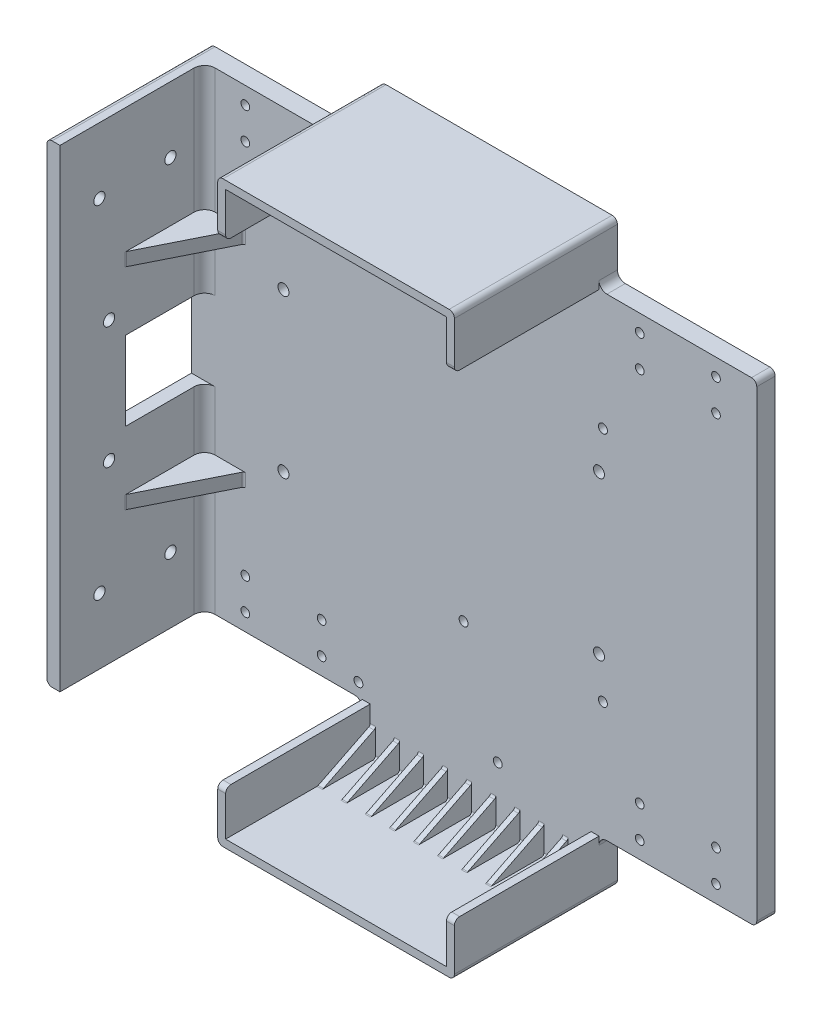
SolidWorks part; units mm, degrees
ref_plane "Front Plane" through (0, 0, 0) normal (0, 0, 1) x (1, 0, 0)
ref_plane "Top Plane" through (0, 0, 0) normal (0, 1, 0) x (1, 0, 0)
ref_plane "Right Plane" through (0, 0, 0) normal (1, 0, 0) x (0, 0, -1)
sketch "Sketch2" plane through (0, 0, 0) normal (0, 0, 1) x (1, 0, 0)
  line L1 (-105, -90) -> (105, -90)
  line L2 (-105, -90) -> (-105, 90)
  line L3 (-105, 90) -> (105, 90)
  line L4 (105, -90) -> (105, 90)
  line L5 (-105, -90) -> (105, 90) construction
  line L6 (-105, 90) -> (105, -90) construction
  point P0 (0, 0)
  dimension "D1" = 210
  dimension "D2" = 180
extrude "Boss-Extrude1" add sketch "Sketch2" along normal blind 7
sketch "Sketch3" plane through (0, -90, 0) normal (0, -1, 0) x (-1, 0, 0)
  line L0 (105, -7) -> (-105, -7) construction
  line L1 (45, -7) -> (-45, -7)
  line L2 (45, -7) -> (45, 0)
  line L3 (45, 0) -> (-45, 0)
  line L4 (-45, -7) -> (-45, 0)
  line L5 (105, 0) -> (-105, 0) construction
  line L6 (105, -7) -> (105, 0) construction
  dimension "D1" = 90
  dimension "D2" = 60
extrude "Boss-Extrude2" add sketch "Sketch3" along normal blind 20
sketch "Sketch4" plane through (0, 90, 0) normal (0, 1, 0) x (1, 0, 0)
  line L0 (105, 0) -> (-105, 0) construction
  line L1 (-45, 0) -> (45, 0)
  line L2 (-45, 0) -> (-45, -7)
  line L3 (-45, -7) -> (45, -7)
  line L4 (45, 0) -> (45, -7)
  line L5 (105, -7) -> (-105, -7) construction
  line L6 (-105, -7) -> (-105, 0) construction
  dimension "D1" = 90
  dimension "D2" = 60
extrude "Boss-Extrude3" add sketch "Sketch4" along normal blind 20
sketch "Sketch5" plane through (0, 0, 7) normal (0, 0, 1) x (1, 0, 0)
  line L0 (105, 90) -> (45, 90) construction
  line L1 (105, -90) -> (105, 90) construction
  line L2 (0, -1000) -> (0, 49000) construction
  line L3 (-1000, 0) -> (49000, 0) construction
  line L4 (-45, 110) -> (45, 110) construction
  line L5 (45, -110) -> (-45, -110) construction
  line L6 (-105, 90) -> (-105, -90) construction
  circle A0 centre (89.5, 83.5) radius 1.65
  circle A2 centre (89.5, 71.5) radius 1.65
  circle A3 centre (60.5, 83.5) radius 1.65
  circle A5 centre (60.5, 71.5) radius 1.65
  circle A6 centre (-60.5, 71.5) radius 1.65
  circle A8 centre (-60.5, 83.5) radius 1.65
  circle A9 centre (-89.5, 71.5) radius 1.65
  circle A11 centre (-89.5, 83.5) radius 1.65
  circle A12 centre (-89.5, -83.5) radius 1.65
  circle A14 centre (-89.5, -71.5) radius 1.65
  circle A15 centre (-60.5, -83.5) radius 1.65
  circle A17 centre (-60.5, -71.5) radius 1.65
  circle A18 centre (60.5, -71.5) radius 1.65
  circle A20 centre (60.5, -83.5) radius 1.65
  circle A21 centre (89.5, -71.5) radius 1.65
  circle A23 centre (89.5, -83.5) radius 1.65
  circle A24 centre (45, 30) radius 2.1
  circle A25 centre (45, -30) radius 2.1
  circle A26 centre (-75, 30) radius 2.1
  circle A27 centre (-75, -30) radius 2.1
  circle A28 centre (-46.5, -85) radius 1.7
  circle A29 centre (-6.5, -45) radius 1.7
  circle A30 centre (6.5, -85) radius 1.7
  circle A31 centre (46.5, -45) radius 1.7
  circle A32 centre (46.5, 45) radius 1.7
  circle A33 centre (6.5, 85) radius 1.7
  circle A34 centre (-6.5, 45) radius 1.7
  circle A35 centre (-46.5, 85) radius 1.7
  dimension "D7" = 3.3
  dimension "D8" = 3.4
  dimension "D9" = 3.3
  dimension "D12" = 60
  dimension "D14" = 4.2
  dimension "D17" = 4.2
  dimension "D20" = 4.2
  dimension "D21" = 4.2
  dimension "D26" = 3.4
  dimension "D29" = 3.4
  dimension "D32" = 3.4
  dimension "D1" = 6.5
  dimension "D2" = 15.5
  dimension "D3" = 58.5
  dimension "D4" = 12
  dimension "D5" = 15.5
  dimension "D6" = 25
  dimension "D11" = 29
  dimension "D13" = 80
  dimension "D15" = 60
  dimension "D16" = 80
  dimension "D18" = 120
  dimension "D19" = 120
  dimension "D22" = 30
  dimension "D23" = 30
  dimension "D24" = 65
  dimension "D25" = 98.5
  dimension "D27" = 25
  dimension "D28" = 98.5
  dimension "D30" = 65
  dimension "D31" = 58.5
  dimension "D10" = 2
extrude "Cut-Extrude1" cut sketch "Sketch5" against normal through all
sketch "Sketch10" plane through (0, 0, 7) normal (0, 0, 1) x (1, 0, 0)
  line L0 (45, 110) -> (45, 90) construction
  line L1 (-105, 90) -> (-110, 90)
  line L2 (-105, 90) -> (-105, -90)
  line L3 (-105, -90) -> (-110, -90)
  line L4 (-110, 90) -> (-110, -90)
  line L5 (-45, 110) -> (45, 110)
  line L6 (-45, 110) -> (-45, 107)
  line L7 (-45, 107) -> (45, 107)
  line L8 (45, 110) -> (45, 107)
  line L9 (-45, -110) -> (-45, -90) construction
  line L10 (45, -110) -> (-45, -110)
  line L11 (45, -110) -> (45, -107)
  line L12 (45, -107) -> (-45, -107)
  line L13 (-45, -110) -> (-45, -107)
  line L15 (-45, 110) -> (-42, 110)
  line L16 (-45, 110) -> (-45, 90)
  line L17 (-45, 90) -> (-42, 90)
  line L18 (-42, 110) -> (-42, 90)
  line L19 (45, 110) -> (42, 110)
  line L20 (45, 110) -> (45, 90)
  line L21 (45, 90) -> (42, 90)
  line L22 (42, 110) -> (42, 90)
  line L23 (-45, -110) -> (-42, -110)
  line L24 (-45, -110) -> (-45, -90)
  line L25 (-45, -90) -> (-42, -90)
  line L26 (-42, -110) -> (-42, -90)
  line L27 (45, -110) -> (42, -110)
  line L28 (45, -110) -> (45, -90)
  line L29 (45, -90) -> (42, -90)
  line L30 (42, -110) -> (42, -90)
  dimension "D1" = 5
  dimension "D2" = 180
  dimension "D3" = 3
  dimension "D4" = 3
  dimension "D5" = 3
  dimension "D6" = 3
  dimension "D7" = 3
  dimension "D8" = 3
  dimension "D9" = 20
  dimension "D10" = 20
  dimension "D11" = 20
  dimension "D12" = 20
extrude "Boss-Extrude4" add sketch "Sketch10" along normal blind 55 contours L2 L1 L4 L3 | L16 L15 L18 L17 | L20 L19 L22 L21 | L6 L5 L8 L7 | L11 L10 L13 L12 | L24 L23 L26 L25 | L28 L27 L30 L29
sketch "Sketch12" plane through (0, 0, 7) normal (0, 0, -1) x (-1, 0, 0)
  line L1 (105, 90) -> (110, 90)
  line L2 (105, 90) -> (105, -90)
  line L3 (105, -90) -> (110, -90)
  line L4 (110, 90) -> (110, -90)
  dimension "D1" = 180
  dimension "D2" = 5
extrude "Boss-Extrude5" add sketch "Sketch12" along normal blind 7 contours L2 L1 L4 L3
fillet "Fillet2" radius 2 1 edges at (-45, 110, 31)
fillet "Fillet10" radius 3 1 edges at (-45, 90, 3.5)
fillet "Fillet11" radius 3 1 edges at (45, 90, 3.5)
fillet "Fillet13" radius 3 1 edges at (45, -90, 3.5)
fillet "Fillet15" radius 3 1 edges at (-45, -90, 3.5)
fillet "Fillet20" radius 2 4 edges at (43.5, -90, 62) (-43.5, -90, 62) (-43.5, 90, 62) (43.5, 90, 62)
ref_plane "Plane1" through (-42, 107, 7) normal (1, 0, 0) x (0, 0, -1)
sketch "Sketch16" plane through (-42, 0, 0) normal (1, 0, 0) x (0, 0, -1)
  line L0 (-27, 107) -> (-7, 97)
  line L1 (-7, 107) -> (-62, 107) construction
  line L2 (-7, 107) -> (-7, 90) construction
  line L3 (-7, 97) -> (-7, 107)
  line L4 (-7, 107) -> (-27, 107)
  dimension "D1" = 20
  dimension "D2" = 10
extrude "Boss-Extrude6" add sketch "Sketch16" along normal blind 2
pattern_linear "LPattern1" count 10 spacing 9.15 along (1, 0, 0) of "Boss-Extrude6"
ref_plane "Plane2" through (0, 0, 0) normal (0, -1, 0) x (-1, 0, 0)
mirror "Mirror1" about plane through (0, 0, 0) normal (0, -1, 0) of "LPattern1"
fillet "Fillet24" radius 4 1 edges at (-105, 0, 7)
sketch "Sketch17" plane through (-105, 0, 0) normal (1, 0, 0) x (0, 0, -1)
  line L0 (-62, 90) -> (-62, -90) construction
  line L1 (-62, -90) -> (-11, -90) construction
  circle A0 centre (-43.32, -23.15) radius 2.15
  dimension "D1" = 4.3
  dimension "D2" = 18.68
  dimension "D3" = 66.85
extrude "Cut-Extrude2" cut sketch "Sketch17" against normal blind 10
mirror "Mirror2" about plane through (0, 0, 0) normal (0, -1, 0) of "Cut-Extrude2"
fillet "Fillet25" radius 1 18 edges at (-36.425, -107, 7) (-27.275, -107, 7) (-18.125, -107, 7) (-8.975, -107, 7) (0.175, -107, 7) (9.325, -107, 7) (18.475, -107, 7) (27.625, -107, 7) (36.775, -107, 7) (-36.425, 107, 7) (-27.275, 107, 7) (-18.125, 107, 7) (-8.975, 107, 7) (0.175, 107, 7) (9.325, 107, 7) (18.475, 107, 7) (27.625, 107, 7) (36.775, 107, 7)
ref_plane "Plane3" through (0, -40, 0) normal (0, -1, 0) x (-1, 0, 0)
ref_plane "Plane4" through (0, 40, 0) normal (0, -1, 0) x (-1, 0, 0)
sketch "Sketch18" plane through (0, -40, 0) normal (0, -1, 0) x (-1, 0, 0)
  line L0 (105, -37) -> (90, -7)
  line L1 (105, -62) -> (105, -11) construction
  line L2 (101, -7) -> (48, -7) construction
  dimension "D1" = 30
  dimension "D2" = 15
rib "Rib1" sketch "Sketch18" sketch "Sketch18" thickness 5 extrusion direction parallel to sketch draft on no parameters "D1"=5
sketch "Sketch19" plane through (0, 40, 0) normal (0, -1, 0) x (-1, 0, 0)
  line L0 (105, -37) -> (90, -7)
  line L1 (105, -62) -> (105, -11) construction
  line L2 (101, -7) -> (48, -7) construction
  dimension "D1" = 15
  dimension "D2" = 30
rib "Rib2" sketch "Sketch19" sketch "Sketch19" thickness 5 extrusion direction parallel to sketch draft on no parameters "D1"=5
fillet "Fillet26" radius 1 20 edges at (41.175, 107, 27) (32.2, 107, 27) (23.05, 107, 27) (13.9, 107, 27) (4.75, 107, 27) (-4.4, 107, 27) (-13.55, 107, 27) (-22.7, 107, 27) (-31.85, 107, 27) (-41, 107, 27) (41.175, -107, 27) (32.2, -107, 27) (23.05, -107, 27) (13.9, -107, 27) (4.75, -107, 27) (-4.4, -107, 27) (-13.55, -107, 27) (-22.7, -107, 27) (-31.85, -107, 27) (-41, -107, 27)
fillet "Fillet27" radius 1 24 edges at (-90, 40, 7) (-105, 40, 37) (-90, -40, 7) (-105, -40, 37) (41.175, 97, 7) (32.2, 97, 7) (23.05, 97, 7) (13.9, 97, 7) (4.75, 97, 7) (-4.4, 97, 7) (-13.55, 97, 7) (-22.7, 97, 7) (-31.85, 97, 7) (-41, 97, 7) (41.175, -97, 7) (32.2, -97, 7) (23.05, -97, 7) (13.9, -97, 7) (4.75, -97, 7) (-4.4, -97, 7) (-13.55, -97, 7) (-22.7, -97, 7) (-31.85, -97, 7) (-41, -97, 7)
sketch "Sketch20" plane through (-105, 0, 0) normal (1, 0, 0) x (0, 0, -1)
  line L0 (-34.1, 0) -> (34.1, 0) construction
  line L1 (-37, -15) -> (-7, -15)
  line L2 (-37, -15) -> (-37, 15)
  line L3 (-37, 15) -> (-7, 15)
  line L4 (-7, -15) -> (-7, 15)
  line L5 (-37, -15) -> (-7, 15) construction
  line L6 (-37, 15) -> (-7, -15) construction
  line L7 (-7, -90) -> (-7, 90) construction
  point P0 (-22, 0)
  dimension "D1" = 30
  dimension "D2" = 30
  dimension "D3" = 0
extrude "Cut-Extrude3" cut sketch "Sketch20" against normal blind 10 and the other way blind 10
sketch "Sketch21" plane through (-105, 0, 0) normal (1, 0, 0) x (0, 0, -1)
  line L0 (-7, -90) -> (-7, 90) construction
  line L1 (-62, -90) -> (-11, -90) construction
  circle A0 centre (-47, -65) radius 2.15
  dimension "D1" = 4.3
  dimension "D2" = 40
  dimension "D3" = 25
extrude "Cut-Extrude4" cut sketch "Sketch21" against normal blind 10
sketch "Sketch22" plane through (-105, 0, 0) normal (1, 0, 0) x (0, 0, -1)
  line L0 (-62, -90) -> (-11, -90) construction
  line L1 (-7, -90) -> (-7, 90) construction
  circle A0 centre (-20, -65) radius 2.15
  dimension "D1" = 4.3
  dimension "D2" = 25
  dimension "D3" = 13
extrude "Cut-Extrude5" cut sketch "Sketch22" against normal blind 10
mirror "Mirror3" about plane through (0, 0, 0) normal (0, -1, 0) of "Cut-Extrude4", "Cut-Extrude5"
fillet "Fillet29" radius 2 5 edges at (-45, -110, 31) (45, -110, 31) (105, -90, 3.5) (105, 90, 3.5) (45, 110, 31)
fillet "Fillet30" radius 2 2 edges at (-110, 90, 31) (-110, -90, 31)
